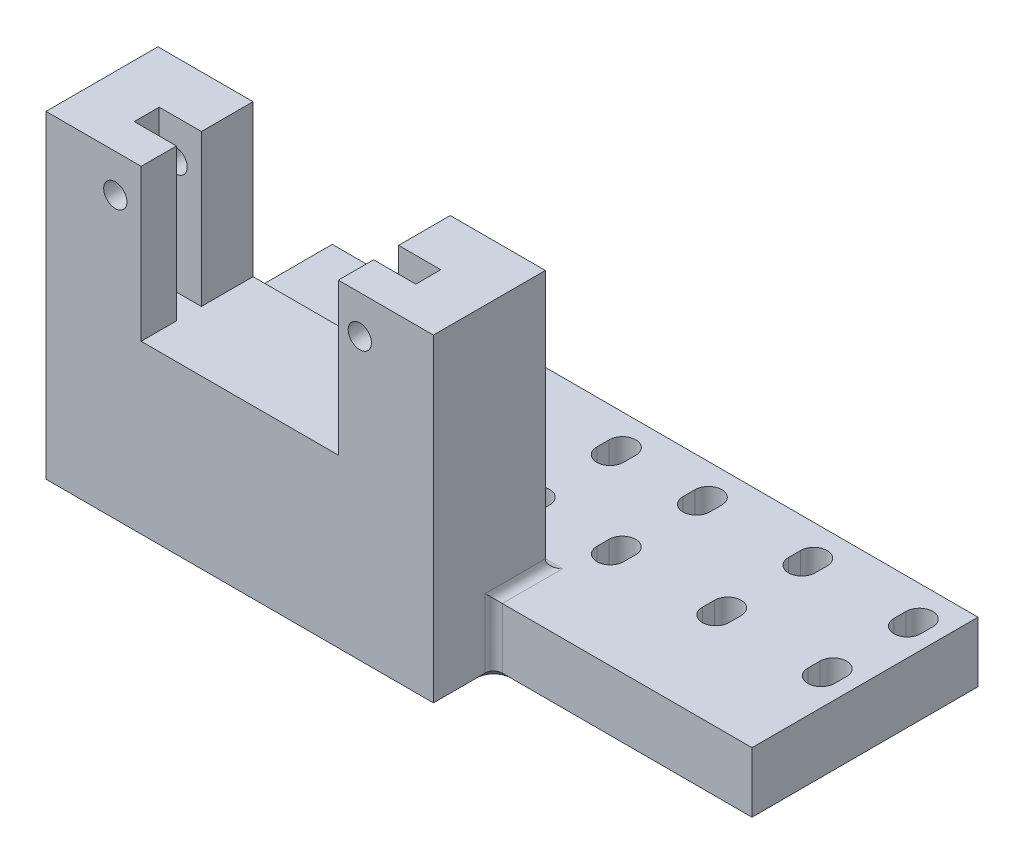
SolidWorks part; units mm, degrees
material "ABS"
ref_plane "Front Plane" through (0, 0, 0) normal (0, 0, 1) x (1, 0, 0)
ref_plane "Top Plane" through (0, 0, 0) normal (0, 1, 0) x (1, 0, 0)
ref_plane "Right Plane" through (0, 0, 0) normal (1, 0, 0) x (0, 0, -1)
sketch "Sketch1" plane through (0, 0, 0) normal (0, 1, 0) x (1, 0, 0)
  line L1 (0, 0) -> (45, 0)
  line L2 (0, 0) -> (0, 6)
  line L3 (0, 6) -> (45, 6)
  line L4 (45, 0) -> (45, 6)
  dimension "D1" = 45
  dimension "D2" = 6
extrude "Boss-Extrude1" add sketch "Sketch1" along normal blind 32
sketch "Sketch2" plane through (0, 0, 0) normal (0, 0, 1) x (1, 0, 0)
  line L0 (0, 32) -> (45, 32) construction
  line L2 (11.05, 32) -> (11.05, 14.4)
  line L3 (11.05, 14.4) -> (33.95, 14.4)
  line L4 (33.95, 32) -> (33.95, 14.4)
  line L5 (11.05, 32) -> (33.95, 32)
  line L6 (22.5, 14.4) -> (22.5, 0) construction
  line L7 (0, 0) -> (45, 0) construction
  dimension "D1" = 22.9
  dimension "D3" = 14.4
extrude "Cut-Extrude1" cut sketch "Sketch2" against normal through all
sketch "Sketch3" plane through (0, 0, 0) normal (0, -1, 0) x (1, 0, 0)
  line L0 (45, 0) -> (45, -6) construction
  line L1 (0, 0) -> (45, 0)
  line L2 (0, 0) -> (0, -24.75)
  line L3 (0, -24.75) -> (45, -24.75)
  line L4 (45, 0) -> (45, -24.75)
  dimension "D1" = 24.75
extrude "Boss-Extrude2" add sketch "Sketch3" along normal blind 6
sketch "Sketch4" plane through (45, 0, 0) normal (1, 0, 0) x (0, 0, -1)
  line L1 (24.75, 0) -> (0, 0)
  line L2 (24.75, 0) -> (24.75, -6)
  line L3 (24.75, -6) -> (0, -6)
  line L4 (0, 0) -> (0, -6)
extrude "Boss-Extrude3" add sketch "Sketch4" along normal blind 30
sketch "Sketch5" plane through (0, -6, 0) normal (0, -1, 0) x (1, 0, 0)
  line L0 (47.2888, -11.95) -> (59.5388, -11.95) construction
  line L1 (37.2888, -21.95) -> (47.2888, -21.95) construction
  line L2 (47.2888, -21.95) -> (59.5388, -21.95) construction
  line L3 (59.5388, -21.95) -> (71.7888, -21.95) construction
  line L4 (71.7888, -21.95) -> (71.7888, -11.95) construction
  line L5 (59.5388, -11.95) -> (59.5388, -21.95) construction
  line L6 (47.2888, -11.95) -> (47.2888, -21.95) construction
  line L7 (0, -24.75) -> (75, -24.75) construction
  line L8 (75, 0) -> (75, -24.75) construction
  line L9 (59.5388, -11.95) -> (71.7888, -11.95) construction
  circle A1 centre (37.2888, -21.95) radius 1.5
  circle A5 centre (47.2888, -21.95) radius 1.5
  circle A7 centre (47.2888, -11.95) radius 1.5
  circle A9 centre (59.5388, -21.95) radius 1.5
  circle A11 centre (71.7888, -21.95) radius 1.5
  circle A13 centre (71.7888, -11.95) radius 1.5
  circle A14 centre (59.5388, -11.95) radius 1.5
  dimension "D1" = 10
  dimension "D2" = 12.25
  dimension "D6" = 3
  dimension "D7" = 3.2112
  dimension "D3" = 12.25
  dimension "D4" = 2.8
  dimension "D5" = 10
extrude "Cut-Extrude2" cut sketch "Sketch5" against normal through all
sketch "Sketch6" plane through (0, 0, 0) normal (0, 0, 1) x (1, 0, 0)
  line L0 (0, -6) -> (0, 32)
  line L1 (0, 32) -> (11.05, 32)
  line L2 (11.05, 32) -> (11.05, 14.4)
  line L3 (11.05, 14.4) -> (33.95, 14.4)
  line L4 (33.95, 14.4) -> (33.95, 32)
  line L5 (33.95, 32) -> (45, 32)
  line L6 (45, 32) -> (45, -6)
  line L7 (75, -6) -> (0, -6) construction
  line L8 (45, -6) -> (-0.8534, -6)
  line M1 (45, 32) -> (33.95, 32)
  line M2 (33.95, 32) -> (33.95, 14.4)
  line M3 (33.95, 14.4) -> (11.05, 14.4)
  line M4 (11.05, 14.4) -> (11.05, 32)
  line M5 (11.05, 32) -> (0, 32)
  line M6 (0, 32) -> (0, -6)
  line M7 (0, -6) -> (75, -6)
  line M10 (45, 0) -> (45, 32)
extrude "Boss-Extrude4" add sketch "Sketch6" along normal blind 7 contours L6 M10 M1 M2 M3 M4 M5 M6 M7 region at (22.5, 9.8545, 0)
sketch "Sketch7" plane through (0, 32, 0) normal (0, 1, 0) x (1, 0, 0)
  line L1 (6.15, 0) -> (38.85, 0)
  line L2 (6.15, 0) -> (6.15, -2.9)
  line L3 (6.15, -2.9) -> (38.85, -2.9)
  line L4 (38.85, 0) -> (38.85, -2.9)
  line L5 (22.5, 6) -> (22.5, 0) construction
  line L6 (11.05, 6) -> (33.95, 6) construction
  dimension "D1" = 2.9
  dimension "D2" = 32.7
extrude "Cut-Extrude3" cut sketch "Sketch7" against normal up to surface (17.6 mm away) up to face at (22.5, 14.4, 0.5)
sketch "Sketch8" plane through (0, 0, 7) normal (0, 0, 1) x (1, 0, 0)
  line L0 (11.05, 32) -> (0, 32) construction
  line L1 (11.05, 14.4) -> (11.05, 32) construction
  line L2 (33.95, 32) -> (33.95, 14.4) construction
  circle A0 centre (8.05, 27.6) radius 1.35
  circle A1 centre (36.45, 27.6) radius 1.35
  dimension "D1" = 2.7
  dimension "D3" = 3
  dimension "D2" = 4.4
  dimension "D4" = 2.5
extrude "Cut-Extrude4" cut sketch "Sketch8" against normal through all
sketch "Sketch9" plane through (0, 0, 0) normal (0, 1, 0) x (1, 0, 0)
  line L6 (0, 6) -> (45, 6)
  line L7 (45, 6) -> (45, 0)
  line L8 (45, 0) -> (75, 0)
  line L9 (75, 0) -> (75, 24.75)
  line L10 (75, 24.75) -> (0, 24.75)
  line L11 (0, 24.75) -> (0, 6)
  line L12 (0, 6) -> (45, 6)
  line L13 (45, 6) -> (45, 0)
  line L14 (45, 0) -> (75, 0)
  line L15 (75, 0) -> (75, 24.75)
  line L16 (75, 24.75) -> (0, 24.75)
  line L17 (0, 24.75) -> (0, 6)
  circle A0 centre (71.7888, 21.95) radius 1.5 construction
  circle A1 centre (59.5388, 21.95) radius 1.5 construction
  circle A2 centre (71.7888, 11.95) radius 1.5 construction
  circle A3 centre (59.5388, 11.95) radius 1.5 construction
  circle A4 centre (47.2888, 11.95) radius 1.5 construction
  circle A5 centre (47.2888, 21.95) radius 1.5 construction
  circle A6 centre (37.2888, 21.95) radius 1.5 construction
  circle A7 centre (71.7888, 21.95) radius 1.5
  circle A8 centre (59.5388, 21.95) radius 1.5
  circle A9 centre (71.7888, 11.95) radius 1.5
  circle A10 centre (59.5388, 11.95) radius 1.5
  circle A11 centre (47.2888, 11.95) radius 1.5
  circle A12 centre (47.2888, 21.95) radius 1.5
  circle A13 centre (37.2888, 21.95) radius 1.5
  dimension "D1" = 0
extrude "Boss-Extrude5" add sketch "Sketch9" along normal blind 2
fillet "Fillet1" radius 1 3 edges at (45, -2, 0) (45, 2, -3) (22.5, 2, -6)
sketch "Sketch11" plane through (0, 0, -24.75) normal (0, 0, -1) x (-1, 0, 0)
  line L4 (0, -6) -> (0, 2)
  line L5 (0, 2) -> (-75, 2)
  line L6 (-75, 2) -> (-75, -6)
  line L7 (-75, -6) -> (0, -6)
  line L8 (0, -6) -> (0, 2)
  line L9 (0, 2) -> (-75, 2)
  line L10 (-75, 2) -> (-75, -6)
  line L11 (-75, -6) -> (0, -6)
  dimension "D1" = 0
extrude "Boss-Extrude7" add sketch "Sketch11" along normal blind 1.5
chamfer "Chamfer1" distance 1 angle 45 7 edges at (0, -6, -9.625) (75, -6, -13.125) (60.5, -6, 0) (45, -6, 4) (22.5, -6, 7) (45.2929, -6, 0.2929) (37.5, -6, -26.25)
sketch "Sketch12" plane through (0, 2, 0) normal (0, 1, 0) x (1, 0, 0)
  line L0 (37.2888, 21.2317) -> (37.2888, 22.6683) construction
  line L1 (35.7377, 21.2317) -> (35.7377, 22.6683)
  line L2 (38.84, 21.2317) -> (38.84, 22.6683)
  arc A0 (35.7377, 21.2317) -> (38.84, 21.2317) centre (37.2888, 21.2317) ccw
  arc A1 (38.84, 22.6683) -> (35.7377, 22.6683) centre (37.2888, 22.6683) ccw
  point P2 (37.2888, 21.95)
  dimension "D1" = 3.1023
  dimension "D2" = 4.5388
extrude "Cut-Extrude5" cut sketch "Sketch12" against normal through all
pattern_linear "LPattern1" count 2 spacing 10 along (0, 0, 1) of "Cut-Extrude5"
sketch "Sketch13" plane through (0, 2, 0) normal (0, 1, 0) x (1, 0, 0)
  line L0 (47.2888, 21.25) -> (47.2888, 22.65) construction
  line L1 (45.7388, 21.25) -> (45.7388, 22.65)
  line L2 (48.8388, 21.25) -> (48.8388, 22.65)
  arc A0 (45.7388, 21.25) -> (48.8388, 21.25) centre (47.2888, 21.25) ccw
  arc A1 (48.8388, 22.65) -> (45.7388, 22.65) centre (47.2888, 22.65) ccw
  point P2 (47.2888, 21.95)
  dimension "D1" = 3.1
  dimension "D2" = 4.5
extrude "Cut-Extrude6" cut sketch "Sketch13" against normal through all
pattern_linear "LPattern2" count 3 spacing 12.25 along (1, 0, 0) count 2 spacing 10 along (0, 0, 1) of "Cut-Extrude6"
